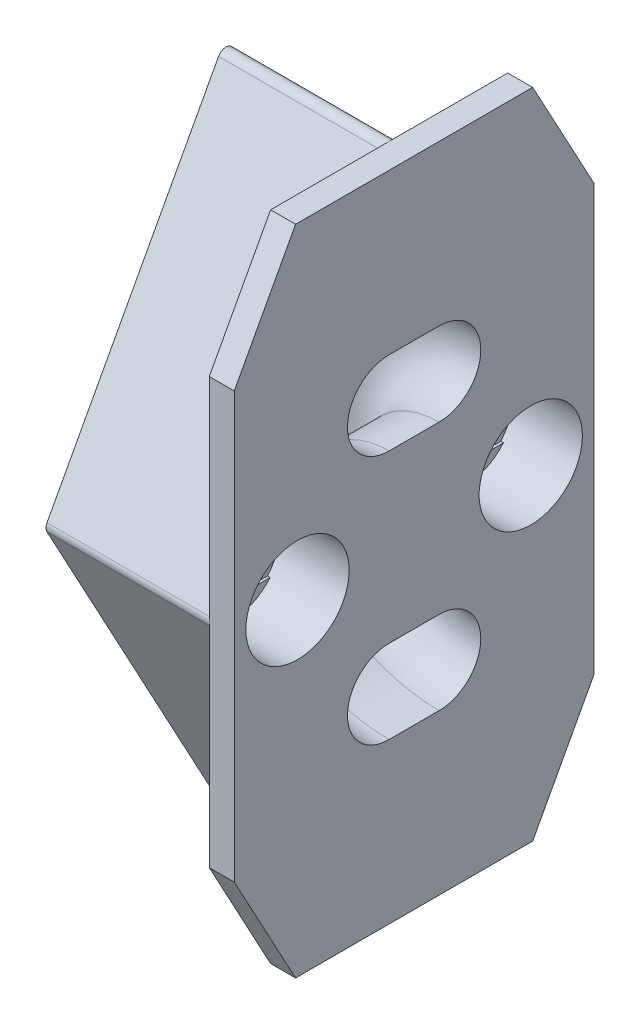
SolidWorks part; units mm, degrees
ref_plane "Front" through (0, 0, 0) normal (0, 0, 1) x (1, 0, 0)
ref_plane "Top" through (0, 0, 0) normal (0, 1, 0) x (1, 0, 0)
ref_plane "Right" through (0, 0, 0) normal (1, 0, 0) x (0, 0, -1)
sketch "Sketch1" plane through (0, 0, 0) normal (1, 0, 0) x (0, 0, -1)
  line L1 (0, -28.2575) -> (15.24, 0)
  line L2 (0, -28.2575) -> (-15.24, 0)
  line L3 (-15.24, 0) -> (0, 28.2575)
  line L4 (15.24, 0) -> (0, 28.2575)
  line L5 (0, -28.2575) -> (0, 28.2575) construction
  line L6 (-15.24, 0) -> (15.24, 0) construction
  point P0 (0, 0)
  dimension "D1" = 30.48
  dimension "D2" = 56.515
extrude "Boss-Extrude1" add sketch "Sketch1" along normal blind 12.446
sketch "Sketch6" plane through (12.446, 0, 0) normal (1, 0, 0) x (0, 0, -1)
  line L14 (-22.4547, 0) -> (0, -41.6347)
  line L15 (0, -41.6347) -> (22.4547, 0)
  line L16 (22.4547, 0) -> (0, 41.6347)
  line L17 (0, 41.6347) -> (-22.4547, 0)
  line L18 (-22.4547, 0) -> (0, -41.6347)
  line L19 (0, -41.6347) -> (22.4547, 0)
  line L20 (22.4547, 0) -> (0, 41.6347)
  line L21 (0, 41.6347) -> (-22.4547, 0)
  dimension "D1" = 6.35
extrude "Boss-Extrude3" add sketch "Sketch6" along normal blind 1.905
fillet "Fillet1" radius 1.905 8 edges at (13.3985, 41.6347, 0) (13.3985, 0, 22.4547) (13.3985, -41.6347, 0) (13.3985, 0, -22.4547) (6.223, -28.2575, 0) (6.223, 0, -15.24) (6.223, 0, 15.24) (6.223, 28.2575, 0)
sketch "Sketch7" plane through (0, 0, 0) normal (0, 1, 0) x (1, 0, 0)
  line L0 (0, 0) -> (25.2725, 0) construction
  line L1 (14.351, 0) -> (14.351, -10.3712) construction
  line L3 (4.826, -1.905) -> (4.826, 1.905) construction
  line L4 (1.651, -1.905) -> (1.651, 1.905)
  line L5 (8.001, -1.905) -> (8.001, 1.905)
  line L6 (14.351, -1.6767) -> (14.351, 1.6767) construction
  arc A1 (1.651, -1.905) -> (8.001, -1.905) centre (4.826, -1.905) ccw
  arc A2 (8.001, 1.905) -> (1.651, 1.905) centre (4.826, 1.905) ccw
  point P7 (4.826, 0)
  dimension "D1" = 6.35
  dimension "D2" = 10.16
  dimension "D3" = 6.35
revolve "Cut-Revolve2" cut sketch "Sketch7" angle 360 about L1
sketch "Sketch8" plane through (14.351, 0, 0) normal (1, 0, 0) x (0, 0, -1)
  line L0 (0, 0) -> (8.89, 0) construction
  line L1 (0, 0) -> (0, 3.2594) construction
  circle A0 centre (8.89, 0) radius 3.937
  circle A1 centre (-8.89, 0) radius 3.937
  dimension "D2" = 7.874
  dimension "D1" = 8.89
extrude "Cut-Extrude3" cut sketch "Sketch8" against normal blind 5.08
sketch "Sketch9" plane through (9.271, 0, 0) normal (1, 0, 0) x (0, 0, -1)
  line L0 (0, 0) -> (0, 4.0921) construction
  circle A0 centre (8.89, 0) radius 2.5527
  circle A1 centre (-8.89, 0) radius 2.5527
  dimension "D1" = 5.1054
extrude "Cut-Extrude4" cut sketch "Sketch9" against normal through all
sketch "Sketch10" [suppressed] plane through (15.875, 0, 0) normal (1, 0, 0) x (0, 0, -1)
  line L0 (0, 0) -> (0, 8.2156) construction
  line L1 (13.6525, 2.7496) -> (8.89, 5.4993)
  line L2 (8.89, 5.4993) -> (4.1275, 2.7496)
  line L3 (4.1275, 2.7496) -> (4.1275, -2.7496)
  line L4 (4.1275, -2.7496) -> (8.89, -5.4993)
  line L5 (8.89, -5.4993) -> (13.6525, -2.7496)
  line L6 (13.6525, -2.7496) -> (13.6525, 2.7496)
  line L7 (-13.6525, -2.7496) -> (-13.6525, 2.7496)
  line L8 (-8.89, -5.4993) -> (-13.6525, -2.7496)
  line L9 (-4.1275, -2.7496) -> (-8.89, -5.4993)
  line L10 (-4.1275, 2.7496) -> (-4.1275, -2.7496)
  line L11 (-8.89, 5.4993) -> (-4.1275, 2.7496)
  line L12 (-13.6525, 2.7496) -> (-8.89, 5.4993)
  circle A0 centre (8.89, 0) radius 4.7625 construction
  circle A1 centre (-8.89, 0) radius 4.7625 construction
  point P1 (13.6525, 0)
  dimension "D1" = 9.525
sketch "Sketch11" [suppressed] plane through (15.621, 0, 0) normal (1, 0, 0) x (0, 0, -1)
  line L0 (0, 0) -> (8.89, 0) construction
  line L1 (0, 0) -> (0, 10.0261) construction
  circle A0 centre (8.89, 0) radius 3.175
  circle A1 centre (-8.89, 0) radius 3.175
  dimension "D2" = 6.35
  dimension "D1" = 8.89
extrude "Cut-Extrude6" [suppressed] cut sketch "Sketch11" against normal through all
sketch "Sketch12" plane through (12.446, 0, 0) normal (-1, 0, 0) x (0, 0, 1)
  line L0 (-14.9806, -13.8581) -> (-14.9806, 13.8581)
  line L1 (-1.6767, -38.5258) -> (-21.9669, -0.9043) construction
  line L2 (-21.9669, 0.9043) -> (-1.6767, 38.5258) construction
  line L4 (14.9806, -13.8581) -> (14.9806, 13.8581)
  line L5 (21.9669, -0.9043) -> (1.6767, -38.5258) construction
  line L6 (1.6767, 38.5258) -> (21.9669, 0.9043) construction
  line L7 (-14.9806, -13.8581) -> (-21.9669, -0.9043)
  line L8 (21.9669, -0.9043) -> (14.9806, -13.8581)
  line L9 (14.9806, 13.8581) -> (21.9669, 0.9043)
  line L10 (-21.9669, 0.9043) -> (-14.9806, 13.8581)
  arc A0 (-14.7523, 0.9043) -> (-14.7523, -0.9043) centre (-13.0756, 0) ccw construction
  arc A3 (21.9669, -0.9043) -> (21.9669, 0.9043) centre (20.2903, 0) ccw construction
  arc A4 (-21.9669, 0.9043) -> (-21.9669, -0.9043) centre (-20.2903, 0) ccw construction
  arc A5 (21.9669, -0.9043) -> (21.9669, 0.9043) centre (20.2903, 0) ccw
  arc A6 (-21.9669, 0.9043) -> (-21.9669, -0.9043) centre (-20.2903, 0) ccw
  arc A8 (14.7523, -0.9043) -> (14.7523, 0.9043) centre (13.0756, 0) ccw construction
  point P7 (-14.9806, 0)
  point P11 (14.9806, 0)
extrude "Cut-Extrude7" cut sketch "Sketch12" against normal through all
sketch "Sketch13" plane through (9.271, 0, 0) normal (1, 0, 0) x (0, 0, -1)
  line L1 (5.8927, 2.5527) -> (11.8873, 2.5527)
  line L3 (5.8927, -2.5527) -> (11.8873, -2.5527)
  line L5 (-11.8873, 2.5527) -> (-5.8927, 2.5527)
  line L7 (-11.8873, -2.5527) -> (-5.8927, -2.5527)
  circle A0 centre (8.89, 0) radius 3.937 construction
  circle A1 centre (8.89, 0) radius 3.937 construction
  circle A2 centre (-8.89, 0) radius 3.937 construction
  circle A3 centre (-8.89, 0) radius 2.5527 construction
  circle A4 centre (8.89, 0) radius 2.5527 construction
  circle A5 centre (-8.89, 0) radius 3.937 construction
  arc A6 (5.8927, 2.5527) -> (5.8927, -2.5527) centre (8.89, 0) ccw
  arc A7 (-11.8873, 2.5527) -> (-11.8873, -2.5527) centre (-8.89, 0) ccw
  arc A8 (-5.8927, -2.5527) -> (-5.8927, 2.5527) centre (-8.89, 0) ccw
  arc A9 (11.8873, -2.5527) -> (11.8873, 2.5527) centre (8.89, 0) ccw
extrude "Cut-Extrude8" cut sketch "Sketch13" against normal blind 0.2
sketch "Sketch14" plane through (9.071, 0, 0) normal (1, 0, 0) x (0, 0, -1)
  line L0 (11.8873, 2.5527) -> (5.8927, 2.5527) construction
  line L1 (6.3373, 2.5527) -> (11.4427, 2.5527)
  line L2 (6.3373, 2.5527) -> (6.3373, -2.5527)
  line L3 (6.3373, -2.5527) -> (11.4427, -2.5527)
  line L4 (11.4427, 2.5527) -> (11.4427, -2.5527)
  line L5 (8.89, -2.5527) -> (11.8873, -2.5527) construction
  line L6 (-5.8927, 2.5527) -> (-11.8873, 2.5527) construction
  line L7 (-11.4427, 2.5527) -> (-6.3373, 2.5527)
  line L8 (-11.4427, 2.5527) -> (-11.4427, -2.5527)
  line L9 (-11.4427, -2.5527) -> (-6.3373, -2.5527)
  line L10 (-6.3373, 2.5527) -> (-6.3373, -2.5527)
  line L11 (-11.8873, -2.5527) -> (-5.8927, -2.5527) construction
  arc A0 (-8.89, 2.5527) -> (-8.89, -2.5527) centre (-8.89, 0) ccw construction
  arc A1 (-8.89, -2.5527) -> (-8.89, 2.5527) centre (-8.89, 0) ccw construction
  arc A2 (8.89, 2.5527) -> (8.89, -2.5527) centre (8.89, 0) ccw construction
  arc A3 (8.89, -2.5527) -> (8.89, 2.5527) centre (8.89, 0) ccw construction
extrude "Cut-Extrude9" cut sketch "Sketch14" against normal blind 0.2
sketch "Sketch15" plane through (0, 0, 0) normal (-1, 0, 0) x (0, 0, 1)
  line L4 (1.6767, 25.1486) -> (14.7523, 0.9043) construction
  line L5 (-14.7523, 0.9043) -> (-1.6767, 25.1486) construction
  line L6 (-14.7523, 0.9043) -> (-1.6767, 25.1486)
  line L7 (1.6767, 25.1486) -> (14.7523, 0.9043)
  line L8 (-13.6345, -0.3014) -> (-0.5589, -24.5458)
  line L9 (0.5589, -24.5458) -> (13.6345, -0.3014)
  line L10 (13.6345, 0.3014) -> (0.5589, 24.5458)
  line L11 (-0.5589, 24.5458) -> (-13.6345, 0.3014)
  line L12 (-13.6345, -0.3014) -> (-0.5589, -24.5458)
  line L13 (0.5589, -24.5458) -> (13.6345, -0.3014)
  line L14 (13.6345, 0.3014) -> (0.5589, 24.5458)
  line L15 (-0.5589, 24.5458) -> (-13.6345, 0.3014)
  line L16 (14.7523, -0.9043) -> (1.6767, -25.1486) construction
  line L17 (-1.6767, -25.1486) -> (-14.7523, -0.9043) construction
  line L18 (-1.6767, -25.1486) -> (-14.7523, -0.9043)
  line L19 (14.7523, -0.9043) -> (1.6767, -25.1486)
  arc A4 (1.6767, 25.1486) -> (-1.6767, 25.1486) centre (0, 24.2443) ccw construction
  arc A5 (1.6767, 25.1486) -> (-1.6767, 25.1486) centre (0, 24.2443) ccw
  arc A6 (14.7523, -0.9043) -> (14.7523, 0.9043) centre (13.0756, 0) ccw construction
  arc A7 (-1.6767, -25.1486) -> (1.6767, -25.1486) centre (0, -24.2443) ccw construction
  arc A8 (-13.6345, 0.3014) -> (-13.6345, -0.3014) centre (-13.0756, 0) ccw
  arc A9 (-0.5589, -24.5458) -> (0.5589, -24.5458) centre (0, -24.2443) ccw
  arc A10 (13.6345, -0.3014) -> (13.6345, 0.3014) centre (13.0756, 0) ccw
  arc A11 (0.5589, 24.5458) -> (-0.5589, 24.5458) centre (0, 24.2443) ccw
  arc A12 (-13.6345, 0.3014) -> (-13.6345, -0.3014) centre (-13.0756, 0) ccw
  arc A13 (-0.5589, -24.5458) -> (0.5589, -24.5458) centre (0, -24.2443) ccw
  arc A14 (13.6345, -0.3014) -> (13.6345, 0.3014) centre (13.0756, 0) ccw
  arc A15 (0.5589, 24.5458) -> (-0.5589, 24.5458) centre (0, 24.2443) ccw
  arc A16 (-14.7523, 0.9043) -> (-14.7523, -0.9043) centre (-13.0756, 0) ccw construction
  arc A17 (-14.7523, 0.9043) -> (-14.7523, -0.9043) centre (-13.0756, 0) ccw
  arc A18 (-1.6767, -25.1486) -> (1.6767, -25.1486) centre (0, -24.2443) ccw
  arc A19 (14.7523, -0.9043) -> (14.7523, 0.9043) centre (13.0756, 0) ccw
  dimension "D1" = 1.27
extrude "Cut-Extrude10" cut sketch "Sketch15" against normal up to surface (12.446 mm away) up to face at (12.446, 15.8904, 0)
sketch "Sketch16" plane through (12.446, 0, 0) normal (-1, 0, 0) x (0, 0, 1)
  line L0 (-9.0366, -24.8793) -> (9.0366, -24.8793)
  line L1 (14.9806, -13.8581) -> (1.6767, -38.5258) construction
  line L2 (0, 0) -> (12.6414, 0) construction
  line L3 (-9.0366, 24.8793) -> (9.0366, 24.8793)
  line L4 (-14.9806, 13.8581) -> (-1.6767, 38.5258) construction
  line L5 (1.6767, 38.5258) -> (14.9806, 13.8581) construction
  line L6 (-1.6767, -38.5258) -> (-14.9806, -13.8581) construction
  line L7 (-9.0366, 24.8793) -> (-1.6767, 38.5258)
  line L8 (1.6767, 38.5258) -> (9.0366, 24.8793)
  line L9 (-1.6767, -38.5258) -> (-9.0366, -24.8793)
  line L10 (9.0366, -24.8793) -> (1.6767, -38.5258)
  line L11 (-13.7106, -16.2129) -> (-13.7106, 16.2129)
  line L12 (0, 0) -> (0, 12.975) construction
  line L13 (-14.9806, -13.8581) -> (-14.9806, 13.8581) construction
  line L14 (-1.6767, -38.5258) -> (-9.0366, -24.8793)
  line L15 (-14.9806, -13.8581) -> (-14.9806, 13.8581)
  line L16 (-14.9806, 13.8581) -> (-13.7106, 16.2129)
  line L17 (-9.0366, 24.8793) -> (-1.6767, 38.5258)
  line L18 (-13.7106, -16.2129) -> (-14.9806, -13.8581)
  line L19 (14.9806, 13.8581) -> (13.7106, 16.2129)
  line L20 (14.9806, -13.8581) -> (14.9806, 13.8581)
  line L21 (13.7106, -16.2129) -> (14.9806, -13.8581)
  line L22 (13.7106, -16.2129) -> (13.7106, 16.2129)
  arc A1 (1.6767, 38.5258) -> (-1.6767, 38.5258) centre (0, 37.6215) ccw construction
  arc A2 (-1.6767, -38.5258) -> (1.6767, -38.5258) centre (0, -37.6215) ccw construction
  arc A3 (1.6767, 38.5258) -> (-1.6767, 38.5258) centre (0, 37.6215) ccw
  arc A4 (-1.6767, -38.5258) -> (1.6767, -38.5258) centre (0, -37.6215) ccw
  arc A7 (-13.6345, 0.3014) -> (-13.6345, -0.3014) centre (-13.0756, 0) ccw construction
  arc A8 (-0.5589, -24.5458) -> (0.5589, -24.5458) centre (0, -24.2443) ccw construction
  point P3 (0, -24.8793)
  point P21 (-13.7106, 0)
  line M8 (-1.6767, 38.5258) -> (-14.9806, 13.8581)
  line M9 (-14.9806, 13.8581) -> (-14.9806, -13.8581)
  line M10 (-14.9806, -13.8581) -> (-1.6767, -38.5258)
  arc M11 (-1.6767, -38.5258) -> (1.6767, -38.5258) centre (0, -37.6215) ccw
  line M12 (1.6767, -38.5258) -> (14.9806, -13.8581)
  line M14 (14.9806, 13.8581) -> (1.6767, 38.5258)
  arc M15 (1.6767, 38.5258) -> (-1.6767, 38.5258) centre (0, 37.6215) ccw
extrude "Cut-Extrude11" cut sketch "Sketch16" against normal through all contours L11 M10 M8 M9 | L3 M8 M14 M15 | L0 M10 M11 M12 | L20 L19 L22 L21 region at (12.446, -30.2815, 0) region at (12.446, 0, -14.329) region at (12.446, 30.2815, 0)
